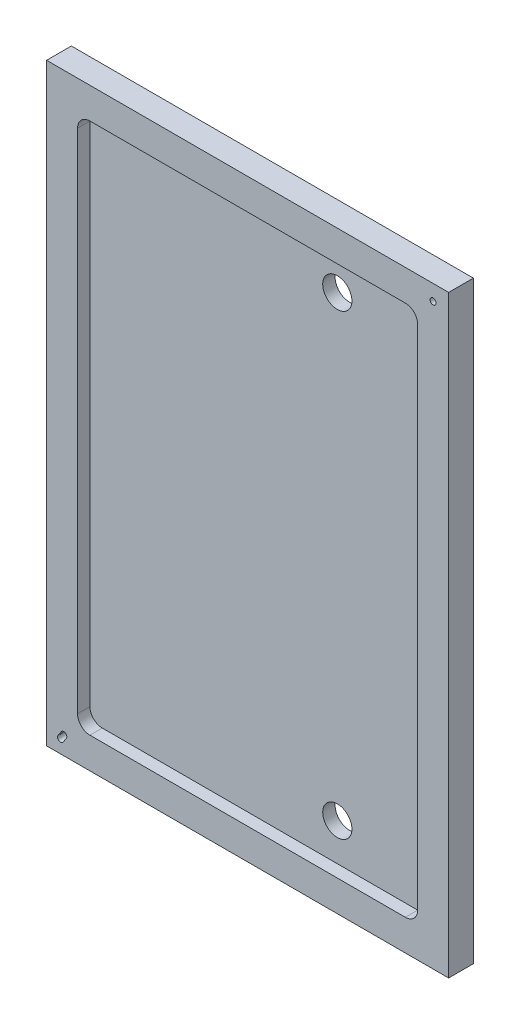
SolidWorks part; units mm, degrees
ref_plane "Front Plane" through (0, 0, 0) normal (0, 0, 1) x (1, 0, 0)
ref_plane "Top Plane" through (0, 0, 0) normal (0, 1, 0) x (1, 0, 0)
ref_plane "Right Plane" through (0, 0, 0) normal (1, 0, 0) x (0, 0, -1)
sketch "Sketch1" plane through (0, 0, 0) normal (0, 0, 1) x (1, 0, 0)
  line L1 (103.1875, -152.4) -> (-103.1875, -152.4)
  line L2 (103.1875, -152.4) -> (103.1875, 152.4)
  line L3 (103.1875, 152.4) -> (-103.1875, 152.4)
  line L4 (-103.1875, -152.4) -> (-103.1875, 152.4)
  line L5 (103.1875, -152.4) -> (-103.1875, 152.4) construction
  line L6 (103.1875, 152.4) -> (-103.1875, -152.4) construction
  point P0 (0, 0)
  dimension "D1" = 304.8
  dimension "D2" = 206.375
extrude "Boss-Extrude1" add sketch "Sketch1" along normal blind 12.7
sketch "Sketch2" plane through (0, 0, 12.7) normal (0, 0, 1) x (1, 0, 0)
  line L0 (-103.1875, 152.4) -> (-103.1875, -152.4) construction
  line L1 (80.9625, -136.525) -> (-80.9625, -136.525)
  line L2 (87.3125, -130.175) -> (87.3125, 130.175)
  line L3 (80.9625, 136.525) -> (-80.9625, 136.525)
  line L4 (-87.3125, -130.175) -> (-87.3125, 130.175)
  line L5 (87.3125, -136.525) -> (-87.3125, 136.525) construction
  line L6 (87.3125, 136.525) -> (-87.3125, -136.525) construction
  line L7 (103.1875, 152.4) -> (-103.1875, 152.4) construction
  arc A0 (-80.9625, -136.525) -> (-87.3125, -130.175) centre (-80.9625, -130.175) cw
  arc A1 (80.9625, -136.525) -> (87.3125, -130.175) centre (80.9625, -130.175) ccw
  arc A2 (87.3125, 130.175) -> (80.9625, 136.525) centre (80.9625, 130.175) ccw
  arc A3 (-80.9625, 136.525) -> (-87.3125, 130.175) centre (-80.9625, 130.175) ccw
  point P0 (0, 0)
  dimension "D3" = 6.35
  dimension "D1" = 15.875
  dimension "D2" = 15.875
extrude "Cut-Extrude1" cut sketch "Sketch2" against normal blind 6.35
sketch "Sketch4" plane through (0, 0, 0) normal (0, 0, -1) x (-1, 0, 0)
  line L0 (103.1875, -152.4) -> (-103.1875, -152.4) construction
  line L1 (-103.1875, -152.4) -> (-103.1875, 152.4) construction
  line L2 (0, 0) -> (-117.2439, 0) construction
  circle A0 centre (-39.6875, -117.4) radius 7.5
  circle A1 centre (-39.6875, 117.4) radius 7.5
  dimension "D1" = 15
  dimension "D2" = 35
  dimension "D3" = 63.5
  dimension "D4" = 0
extrude "Cut-Extrude3" cut sketch "Sketch4" against normal through all
hole_wizard "Ø3.1 (3.1) Diameter Hole1" positions "Sketch7" profile "Sketch8" hole size "Ø3.1" standard "ANSI Metric"
sketch "Sketch7" plane through (0, 0, 12.7) normal (0, 0, 1) x (1, 0, 0)
  line L0 (103.1875, -152.4) -> (103.1875, 152.4) construction
  line L1 (103.1875, 152.4) -> (-103.1875, 152.4) construction
  point P0 (95.1875, 144.4)
  dimension "D1" = 8
  dimension "D2" = 8
sketch "Sketch8" plane through (95.1875, 144.4, 12.7) normal (1, 0, 0) x (0, -1, 0)
  line L0 (0, 0) -> (0, 5.9313)
  line L1 (0, 5.9313) -> (1.55, 5)
  line L2 (1.55, 5) -> (1.55, 0)
  line L5 (1.55, 0) -> (0, 0)
  line L10 (0, 5.9313) -> (-1.55, 5) construction
  line L11 (0, -6.35) -> (0, 107.95) construction
  dimension "Hole Dia." = 3.1
  dimension "Hole Depth" = 5
  dimension "Drill Angle" = 118
sketch "Sketch9" plane through (0, 0, 12.7) normal (0, 0, 1) x (1, 0, 0)
  line L0 (-96.0154, -145.6508) -> (-94.3596, -143.1492) construction
  line L1 (-97.3079, -144.7953) -> (-95.6521, -142.2937)
  line L2 (-94.7229, -146.5063) -> (-93.0671, -144.0047)
  line L3 (-103.1875, -152.4) -> (103.1875, -152.4) construction
  line L4 (-103.1875, 152.4) -> (-103.1875, -152.4) construction
  arc A0 (-97.3079, -144.7953) -> (-94.7229, -146.5063) centre (-96.0154, -145.6508) ccw
  arc A1 (-93.0671, -144.0047) -> (-95.6521, -142.2937) centre (-94.3596, -143.1492) ccw
  point P4 (-95.1875, -144.4)
  dimension "D1" = 3.1
  dimension "D2" = 8
  dimension "D3" = 8
  dimension "D4" = 3
  dimension "D5" = 56.5
extrude "Cut-Extrude4" cut sketch "Sketch9" against normal blind 5
hole_wizard "M4x0.7 Tapped Hole1" positions "Sketch10" profile "Sketch11" tap size "M4x0.7" standard "ANSI Metric"
sketch "Sketch10" plane through (0, 0, 0) normal (0, 0, -1) x (-1, 0, 0)
  line L0 (103.1875, 152.4) -> (103.1875, -152.4) construction
  line L1 (-103.1875, 152.4) -> (103.1875, 152.4) construction
  point P0 (95.1875, -113.6)
  point P2 (95.1875, 113.6)
  dimension "D1" = 8
  dimension "D2" = 38.8
  dimension "D3" = 266
sketch "Sketch11" plane through (-95.1875, -113.6, 0) normal (1, 0, 0) x (0, 1, 0)
  line L0 (0, 0) -> (0, 6.3914)
  line L1 (0, 6.3914) -> (1.65, 5.4)
  line L2 (1.65, 5.4) -> (1.65, 0)
  line L5 (1.65, 0) -> (0, 0)
  line L10 (0, 6.3914) -> (-1.65, 5.4) construction
  line L11 (0, -6.35) -> (0, 107.95) construction
  dimension "Tap Drill Dia." = 3.3
  dimension "Tap Drill Depth" = 5.4
  dimension "Drill Angle" = 118
cosmetic thread "Hole Thread1" parameters "D1"=3, "D2"=4
cosmetic thread "Hole Thread2" parameters "D1"=3, "D2"=4
